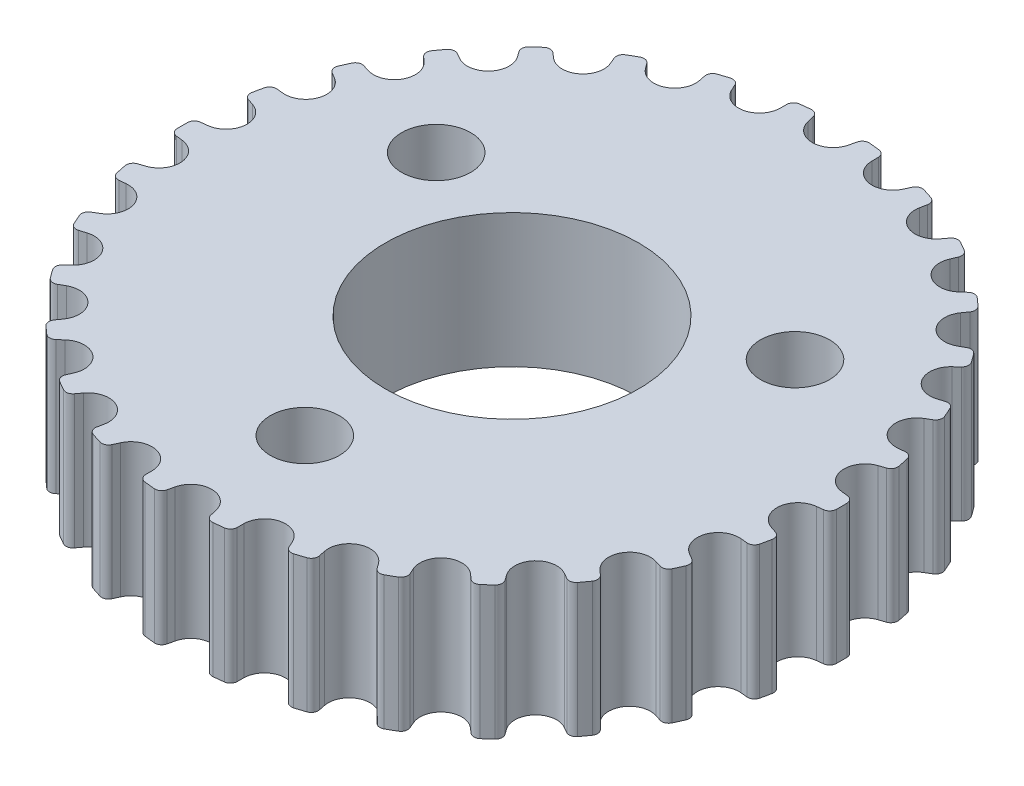
SolidWorks part; units mm, degrees
material "Acrylic (Medium-high impact)"
ref_plane "Front Plane" through (0, 0, 0) normal (0, 0, 1) x (1, 0, 0)
ref_plane "Top Plane" through (0, 0, 0) normal (0, 1, 0) x (1, 0, 0)
ref_plane "Right Plane" through (0, 0, 0) normal (1, 0, 0) x (0, 0, -1)
sketch "Sketch1" plane through (0, 0, 0) normal (0, 1, 0) x (1, 0, 0)
  circle A0 centre (0, 0) radius 14.3239
  dimension "D1" = 28.6479
extrude "Boss-Extrude1" add sketch "Sketch1" along normal blind 5.8
sketch "Sketch2" plane through (0, 5.8, 0) normal (0, 1, 0) x (1, 0, 0)
  line L0 (0, 0) -> (0, 14.3239) construction
  line L1 (-0.8883, 13.7564) -> (-0.95, 14.0339)
  line L2 (-2.9781, 14.0109) -> (-2.9781, 14.3239)
  line L3 (-2.9781, 14.3239) -> (2.9781, 14.3239)
  line L4 (0.8883, 13.7564) -> (0.95, 14.0339)
  line L5 (2.9781, 14.0109) -> (2.9781, 14.3239)
  circle A0 centre (0, 0) radius 14.3239 construction
  arc A1 (0.8883, 13.7564) -> (-0.8883, 13.7564) centre (0, 13.9539) cw
  arc A2 (-0.95, 14.0339) -> (-1.2694, 14.2676) centre (-1.2428, 13.9688) ccw
  arc A4 (0.95, 14.0339) -> (1.2694, 14.2676) centre (1.2428, 13.9688) cw
  arc A5 (-1.2694, 14.2676) -> (-2.9781, 14.0109) centre (0, 0) ccw
  arc A6 (1.2694, 14.2676) -> (2.9781, 14.0109) centre (0, 0) cw
  circle A8 centre (0, 0) radius 14.3239 construction
  point P11 (0, 14.3239)
  point P19 (0, 13.0439)
  dimension "D3" = 0.3
  dimension "D5" = 0.91
  dimension "D2" = 0.95
  dimension "D4" = 1.28
  dimension "D6" = 12
extrude "Cut-Extrude1" cut sketch "Sketch2" against normal through all
pattern_circular "CirPattern1" count 30 over 360 about axis through (0, 5.8, 0) along (0, -1, 0) of "Cut-Extrude1"
sketch "Sketch3" plane through (0, 0, 0) normal (0, -1, 0) x (1, 0, 0)
  circle A0 centre (0, 0) radius 5.5
  dimension "D1" = 11
extrude "Cut-Extrude2" cut sketch "Sketch3" against normal through all
sketch "Sketch4" plane through (0, 0, 0) normal (0, -1, 0) x (1, 0, 0)
  line L0 (0, 0) -> (0, 9) construction
  circle A0 centre (0, 9) radius 1.5
  circle A1 centre (7.7942, -4.5) radius 1.5
  circle A2 centre (-7.7942, -4.5) radius 1.5
  point P14 (0, 0)
  dimension "D1" = 3
  dimension "D2" = 9
  dimension "D3" = 3
extrude "Cut-Extrude3" cut sketch "Sketch4" against normal through all
sketch "Sketch5" plane through (0, 0, 0) normal (0, -1, 0) x (1, 0, 0)
  line L60 (8.7383, -10.682) -> (8.9513, -10.8702)
  line L61 (8.7383, -10.682) -> (8.9513, -10.8702)
  line L62 (9.875, -10.0385) -> (9.7101, -9.807)
  line L63 (9.875, -10.0385) -> (9.7101, -9.807)
  line L64 (12.5987, 6.2896) -> (12.3276, 6.2043)
  line L65 (12.5987, 6.2896) -> (12.3276, 6.2043)
  line L66 (11.5369, 7.5738) -> (11.7463, 7.766)
  line L67 (11.5369, 7.5738) -> (11.7463, 7.766)
  line L68 (-3.638, 13.3126) -> (-3.7561, 13.5712)
  line L69 (-3.638, 13.3126) -> (-3.7561, 13.5712)
  line L70 (-4.9382, 13.1871) -> (-4.8817, 12.9085)
  line L71 (-4.9382, 13.1871) -> (-4.8817, 12.9085)
  line L72 (-11.7463, 7.766) -> (-11.5369, 7.5738)
  line L73 (-11.7463, 7.766) -> (-11.5369, 7.5738)
  line L74 (-12.3276, 6.2043) -> (-12.5987, 6.2896)
  line L75 (-12.3276, 6.2043) -> (-12.5987, 6.2896)
  line L76 (-13.1043, 5.1541) -> (-12.8594, 5.0097)
  line L77 (-13.1043, 5.1541) -> (-12.8594, 5.0097)
  line L78 (-13.3481, 3.5057) -> (-13.6311, 3.5327)
  line L79 (-13.3481, 3.5057) -> (-13.6311, 3.5327)
  line L80 (-13.8895, 2.3169) -> (-13.62, 2.2266)
  line L81 (-13.8895, 2.3169) -> (-13.62, 2.2266)
  line L82 (-13.7853, 0.6538) -> (-14.0677, 0.6215)
  line L83 (-13.7853, 0.6538) -> (-14.0677, 0.6215)
  line L84 (-14.0677, -0.6215) -> (-13.7853, -0.6538)
  line L85 (-14.0677, -0.6215) -> (-13.7853, -0.6538)
  line L86 (-13.62, -2.2266) -> (-13.8895, -2.3169)
  line L87 (-13.62, -2.2266) -> (-13.8895, -2.3169)
  line L88 (-13.6311, -3.5327) -> (-13.3481, -3.5057)
  line L89 (-13.6311, -3.5327) -> (-13.3481, -3.5057)
  line L90 (-12.8594, -5.0097) -> (-13.1043, -5.1541)
  line L91 (-12.8594, -5.0097) -> (-13.1043, -5.1541)
  line L92 (-12.5987, -6.2896) -> (-12.3276, -6.2043)
  line L93 (-12.5987, -6.2896) -> (-12.3276, -6.2043)
  line L94 (-11.5369, -7.5738) -> (-11.7463, -7.766)
  line L95 (-11.5369, -7.5738) -> (-11.7463, -7.766)
  line L96 (-11.0157, -8.7716) -> (-10.7682, -8.6318)
  line L97 (-11.0157, -8.7716) -> (-10.7682, -8.6318)
  line L98 (-9.7101, -9.807) -> (-9.875, -10.0385)
  line L99 (-9.7101, -9.807) -> (-9.875, -10.0385)
  line L100 (-8.9513, -10.8702) -> (-8.7383, -10.682)
  line L101 (-8.9513, -10.8702) -> (-8.7383, -10.682)
  line L102 (-7.4589, -11.6115) -> (-7.5721, -11.8722)
  line L103 (-7.4589, -11.6115) -> (-7.5721, -11.8722)
  line L104 (-6.4956, -12.4937) -> (-6.3264, -12.2653)
  line L105 (-6.4956, -12.4937) -> (-6.3264, -12.2653)
  line L106 (-4.8817, -12.9085) -> (-4.9382, -13.1871)
  line L107 (-4.8817, -12.9085) -> (-4.9382, -13.1871)
  line L108 (-3.7561, -13.5712) -> (-3.638, -13.3126)
  line L109 (-3.7561, -13.5712) -> (-3.638, -13.3126)
  line L110 (-2.0912, -13.6414) -> (-2.0886, -13.9257)
  line L111 (-2.0912, -13.6414) -> (-2.0886, -13.9257)
  line L120 (6.3264, -12.2653) -> (6.4956, -12.4937)
  line L121 (7.5721, -11.8722) -> (7.4589, -11.6115)
  line L124 (10.7682, -8.6318) -> (11.0157, -8.7716)
  line L125 (11.7463, -7.766) -> (11.5369, -7.5738)
  line L126 (12.3276, -6.2043) -> (12.5987, -6.2896)
  line L127 (13.1043, -5.1541) -> (12.8594, -5.0097)
  line L128 (13.3481, -3.5057) -> (13.6311, -3.5327)
  line L129 (13.8895, -2.3169) -> (13.62, -2.2266)
  line L130 (13.7853, -0.6538) -> (14.0677, -0.6215)
  line L131 (14.0677, 0.6215) -> (13.7853, 0.6538)
  line L132 (13.62, 2.2266) -> (13.8895, 2.3169)
  line L133 (13.6311, 3.5327) -> (13.3481, 3.5057)
  line L134 (12.8594, 5.0097) -> (13.1043, 5.1541)
  line L137 (11.0157, 8.7716) -> (10.7682, 8.6318)
  line L138 (9.7101, 9.807) -> (9.875, 10.0385)
  line L139 (8.9513, 10.8702) -> (8.7383, 10.682)
  line L140 (7.4589, 11.6115) -> (7.5721, 11.8722)
  line L141 (6.4956, 12.4937) -> (6.3264, 12.2653)
  line L142 (4.8817, 12.9085) -> (4.9382, 13.1871)
  line L143 (3.7561, 13.5712) -> (3.638, 13.3126)
  line L144 (2.0912, 13.6414) -> (2.0886, 13.9257)
  line L145 (0.8524, 14.0556) -> (0.7907, 13.7781)
  line L146 (-0.7907, 13.7781) -> (-0.8524, 14.0556)
  line L147 (-2.0886, 13.9257) -> (-2.0912, 13.6414)
  line L150 (-6.3264, 12.2653) -> (-6.4956, 12.4937)
  line L151 (-7.5721, 11.8722) -> (-7.4589, 11.6115)
  line L152 (-8.7383, 10.682) -> (-8.9513, 10.8702)
  line L153 (-9.875, 10.0385) -> (-9.7101, 9.807)
  line L154 (-10.7682, 8.6318) -> (-11.0157, 8.7716)
  line L175 (-0.8524, -14.0556) -> (-0.7907, -13.7781)
  line L176 (0.7907, -13.7781) -> (0.8524, -14.0556)
  line L177 (2.0886, -13.9257) -> (2.0912, -13.6414)
  line L178 (3.638, -13.3126) -> (3.7561, -13.5712)
  line L179 (4.9382, -13.1871) -> (4.8817, -12.9085)
  line L180 (6.3264, -12.2653) -> (6.4956, -12.4937)
  line L181 (7.5721, -11.8722) -> (7.4589, -11.6115)
  line L184 (10.7682, -8.6318) -> (11.0157, -8.7716)
  line L185 (11.7463, -7.766) -> (11.5369, -7.5738)
  line L186 (12.3276, -6.2043) -> (12.5987, -6.2896)
  line L187 (13.1043, -5.1541) -> (12.8594, -5.0097)
  line L188 (13.3481, -3.5057) -> (13.6311, -3.5327)
  line L189 (13.8895, -2.3169) -> (13.62, -2.2266)
  line L190 (13.7853, -0.6538) -> (14.0677, -0.6215)
  line L191 (14.0677, 0.6215) -> (13.7853, 0.6538)
  line L192 (13.62, 2.2266) -> (13.8895, 2.3169)
  line L193 (13.6311, 3.5327) -> (13.3481, 3.5057)
  line L194 (12.8594, 5.0097) -> (13.1043, 5.1541)
  line L197 (11.0157, 8.7716) -> (10.7682, 8.6318)
  line L198 (9.7101, 9.807) -> (9.875, 10.0385)
  line L199 (8.9513, 10.8702) -> (8.7383, 10.682)
  line L200 (7.4589, 11.6115) -> (7.5721, 11.8722)
  line L201 (6.4956, 12.4937) -> (6.3264, 12.2653)
  line L202 (4.8817, 12.9085) -> (4.9382, 13.1871)
  line L203 (3.7561, 13.5712) -> (3.638, 13.3126)
  line L204 (2.0912, 13.6414) -> (2.0886, 13.9257)
  line L205 (0.8524, 14.0556) -> (0.7907, 13.7781)
  line L206 (-0.7907, 13.7781) -> (-0.8524, 14.0556)
  line L207 (-2.0886, 13.9257) -> (-2.0912, 13.6414)
  line L210 (-6.3264, 12.2653) -> (-6.4956, 12.4937)
  line L211 (-7.5721, 11.8722) -> (-7.4589, 11.6115)
  line L212 (-8.7383, 10.682) -> (-8.9513, 10.8702)
  line L213 (-9.875, 10.0385) -> (-9.7101, 9.807)
  line L214 (-10.7682, 8.6318) -> (-11.0157, 8.7716)
  line L235 (-0.8524, -14.0556) -> (-0.7907, -13.7781)
  line L236 (0.7907, -13.7781) -> (0.8524, -14.0556)
  line L237 (2.0886, -13.9257) -> (2.0912, -13.6414)
  line L238 (3.638, -13.3126) -> (3.7561, -13.5712)
  line L239 (4.9382, -13.1871) -> (4.8817, -12.9085)
  arc A76 (8.9513, -10.8702) -> (9.479, -10.8719) centre (9.2161, -10.5704) ccw
  arc A77 (8.9513, -10.8702) -> (9.479, -10.8719) centre (9.2161, -10.5704) ccw
  arc A78 (9.479, -10.8719) -> (9.8216, -10.5635) centre (0, 0) ccw
  arc A79 (9.479, -10.8719) -> (9.8216, -10.5635) centre (0, 0) ccw
  arc A80 (9.8216, -10.5635) -> (9.875, -10.0385) centre (9.5492, -10.2705) ccw
  arc A81 (9.8216, -10.5635) -> (9.875, -10.0385) centre (9.5492, -10.2705) ccw
  circle A120 centre (0, 0) radius 13.0439
  arc A121 (-0.8883, 13.7564) -> (0.8883, 13.7564) centre (0, 13.9539) ccw construction
  arc A128 (11.5369, 7.5738) -> (12.3276, 6.2043) centre (12.0845, 6.977) ccw
  arc A129 (11.5369, 7.5738) -> (12.3276, 6.2043) centre (12.0845, 6.977) ccw
  arc A130 (-3.7561, 13.5712) -> (-4.2375, 13.7875) centre (-4.12, 13.4051) ccw
  arc A131 (-3.7561, 13.5712) -> (-4.2375, 13.7875) centre (-4.12, 13.4051) ccw
  arc A132 (-4.2375, 13.7875) -> (-4.6759, 13.645) centre (0, 0) ccw
  arc A133 (-4.2375, 13.7875) -> (-4.6759, 13.645) centre (0, 0) ccw
  arc A134 (-4.6759, 13.645) -> (-4.9382, 13.1871) centre (-4.5462, 13.2666) ccw
  arc A135 (-4.6759, 13.645) -> (-4.9382, 13.1871) centre (-4.5462, 13.2666) ccw
  arc A136 (-11.8032, 8.2906) -> (-11.7463, 7.766) centre (-11.4759, 8.0607) ccw
  arc A137 (-11.8032, 8.2906) -> (-11.7463, 7.766) centre (-11.4759, 8.0607) ccw
  arc A138 (-12.3276, 6.2043) -> (-11.5369, 7.5738) centre (-12.0845, 6.977) ccw
  arc A139 (-12.3276, 6.2043) -> (-11.5369, 7.5738) centre (-12.0845, 6.977) ccw
  arc A140 (-12.5987, 6.2896) -> (-13.0815, 6.0766) centre (-12.7187, 5.908) ccw
  arc A141 (-12.5987, 6.2896) -> (-13.0815, 6.0766) centre (-12.7187, 5.908) ccw
  arc A142 (-13.0815, 6.0766) -> (-13.269, 5.6554) centre (0, 0) ccw
  arc A143 (-13.0815, 6.0766) -> (-13.269, 5.6554) centre (0, 0) ccw
  arc A144 (-13.269, 5.6554) -> (-13.1043, 5.1541) centre (-12.901, 5.4986) ccw
  arc A145 (-13.269, 5.6554) -> (-13.1043, 5.1541) centre (-12.901, 5.4986) ccw
  arc A146 (-13.3481, 3.5057) -> (-12.8594, 5.0097) centre (-13.271, 4.312) ccw
  arc A147 (-13.3481, 3.5057) -> (-12.8594, 5.0097) centre (-13.271, 4.312) ccw
  arc A148 (-13.6311, 3.5327) -> (-14.059, 3.224) centre (-13.6691, 3.1346) ccw
  arc A149 (-13.6311, 3.5327) -> (-14.059, 3.224) centre (-13.6691, 3.1346) ccw
  arc A150 (-14.059, 3.224) -> (-14.1549, 2.7731) centre (0, 0) ccw
  arc A151 (-14.059, 3.224) -> (-14.1549, 2.7731) centre (0, 0) ccw
  arc A152 (-14.1549, 2.7731) -> (-13.8895, 2.3169) centre (-13.7623, 2.6962) ccw
  arc A153 (-14.1549, 2.7731) -> (-13.8895, 2.3169) centre (-13.7623, 2.6962) ccw
  arc A154 (-13.7853, 0.6538) -> (-13.62, 2.2266) centre (-13.8775, 1.4586) ccw
  arc A155 (-13.7853, 0.6538) -> (-13.62, 2.2266) centre (-13.8775, 1.4586) ccw
  arc A156 (-14.0677, 0.6215) -> (-14.4221, 0.2305) centre (-14.0222, 0.2241) ccw
  arc A157 (-14.0677, 0.6215) -> (-14.4221, 0.2305) centre (-14.0222, 0.2241) ccw
  arc A158 (-14.4221, 0.2305) -> (-14.4221, -0.2305) centre (0, 0) ccw
  arc A159 (-14.4221, 0.2305) -> (-14.4221, -0.2305) centre (0, 0) ccw
  arc A160 (-14.4221, -0.2305) -> (-14.0677, -0.6215) centre (-14.0222, -0.2241) ccw
  arc A161 (-14.4221, -0.2305) -> (-14.0677, -0.6215) centre (-14.0222, -0.2241) ccw
  arc A162 (-13.62, -2.2266) -> (-13.7853, -0.6538) centre (-13.8775, -1.4586) ccw
  arc A163 (-13.62, -2.2266) -> (-13.7853, -0.6538) centre (-13.8775, -1.4586) ccw
  arc A164 (-13.8895, -2.3169) -> (-14.1549, -2.7731) centre (-13.7623, -2.6962) ccw
  arc A165 (-13.8895, -2.3169) -> (-14.1549, -2.7731) centre (-13.7623, -2.6962) ccw
  arc A166 (-14.1549, -2.7731) -> (-14.059, -3.224) centre (0, 0) ccw
  arc A167 (-14.1549, -2.7731) -> (-14.059, -3.224) centre (0, 0) ccw
  arc A168 (-14.059, -3.224) -> (-13.6311, -3.5327) centre (-13.6691, -3.1346) ccw
  arc A169 (-14.059, -3.224) -> (-13.6311, -3.5327) centre (-13.6691, -3.1346) ccw
  arc A170 (-12.8594, -5.0097) -> (-13.3481, -3.5057) centre (-13.271, -4.312) ccw
  arc A171 (-12.8594, -5.0097) -> (-13.3481, -3.5057) centre (-13.271, -4.312) ccw
  arc A172 (-13.1043, -5.1541) -> (-13.269, -5.6554) centre (-12.901, -5.4986) ccw
  arc A173 (-13.1043, -5.1541) -> (-13.269, -5.6554) centre (-12.901, -5.4986) ccw
  arc A174 (-13.269, -5.6554) -> (-13.0815, -6.0766) centre (0, 0) ccw
  arc A175 (-13.269, -5.6554) -> (-13.0815, -6.0766) centre (0, 0) ccw
  arc A176 (-13.0815, -6.0766) -> (-12.5987, -6.2896) centre (-12.7187, -5.908) ccw
  arc A177 (-13.0815, -6.0766) -> (-12.5987, -6.2896) centre (-12.7187, -5.908) ccw
  arc A178 (-11.5369, -7.5738) -> (-12.3276, -6.2043) centre (-12.0845, -6.977) ccw
  arc A179 (-11.5369, -7.5738) -> (-12.3276, -6.2043) centre (-12.0845, -6.977) ccw
  arc A180 (-11.7463, -7.766) -> (-11.8032, -8.2906) centre (-11.4759, -8.0607) ccw
  arc A181 (-11.7463, -7.766) -> (-11.8032, -8.2906) centre (-11.4759, -8.0607) ccw
  arc A182 (-11.8032, -8.2906) -> (-11.5323, -8.6636) centre (0, 0) ccw
  arc A183 (-11.8032, -8.2906) -> (-11.5323, -8.6636) centre (0, 0) ccw
  arc A184 (-11.5323, -8.6636) -> (-11.0157, -8.7716) centre (-11.2124, -8.4233) ccw
  arc A185 (-11.5323, -8.6636) -> (-11.0157, -8.7716) centre (-11.2124, -8.4233) ccw
  arc A186 (-9.7101, -9.807) -> (-10.7682, -8.6318) centre (-10.3698, -9.337) ccw
  arc A187 (-9.7101, -9.807) -> (-10.7682, -8.6318) centre (-10.3698, -9.337) ccw
  arc A188 (-9.875, -10.0385) -> (-9.8216, -10.5635) centre (-9.5492, -10.2705) ccw
  arc A189 (-9.875, -10.0385) -> (-9.8216, -10.5635) centre (-9.5492, -10.2705) ccw
  arc A190 (-9.8216, -10.5635) -> (-9.479, -10.8719) centre (0, 0) ccw
  arc A191 (-9.8216, -10.5635) -> (-9.479, -10.8719) centre (0, 0) ccw
  arc A192 (-9.479, -10.8719) -> (-8.9513, -10.8702) centre (-9.2161, -10.5704) ccw
  arc A193 (-9.479, -10.8719) -> (-8.9513, -10.8702) centre (-9.2161, -10.5704) ccw
  arc A194 (-7.4589, -11.6115) -> (-8.7383, -10.682) centre (-8.2019, -11.289) ccw
  arc A195 (-7.4589, -11.6115) -> (-8.7383, -10.682) centre (-8.2019, -11.289) ccw
  arc A196 (-7.5721, -11.8722) -> (-7.4107, -12.3747) centre (-7.2051, -12.0315) ccw
  arc A197 (-7.5721, -11.8722) -> (-7.4107, -12.3747) centre (-7.2051, -12.0315) ccw
  arc A198 (-7.4107, -12.3747) -> (-7.0114, -12.6052) centre (0, 0) ccw
  arc A199 (-7.4107, -12.3747) -> (-7.0114, -12.6052) centre (0, 0) ccw
  arc A200 (-7.0114, -12.6052) -> (-6.4956, -12.4937) centre (-6.817, -12.2556) ccw
  arc A201 (-7.0114, -12.6052) -> (-6.4956, -12.4937) centre (-6.817, -12.2556) ccw
  arc A202 (-4.8817, -12.9085) -> (-6.3264, -12.2653) centre (-5.6756, -12.7476) ccw
  arc A203 (-4.8817, -12.9085) -> (-6.3264, -12.2653) centre (-5.6756, -12.7476) ccw
  arc A204 (-4.9382, -13.1871) -> (-4.6759, -13.645) centre (-4.5462, -13.2666) ccw
  arc A205 (-4.9382, -13.1871) -> (-4.6759, -13.645) centre (-4.5462, -13.2666) ccw
  arc A206 (-4.6759, -13.645) -> (-4.2375, -13.7875) centre (0, 0) ccw
  arc A207 (-4.6759, -13.645) -> (-4.2375, -13.7875) centre (0, 0) ccw
  arc A208 (-4.2375, -13.7875) -> (-3.7561, -13.5712) centre (-4.12, -13.4051) ccw
  arc A209 (-4.2375, -13.7875) -> (-3.7561, -13.5712) centre (-4.12, -13.4051) ccw
  arc A210 (-2.0912, -13.6414) -> (-3.638, -13.3126) centre (-2.9012, -13.649) ccw
  arc A211 (-2.0912, -13.6414) -> (-3.638, -13.3126) centre (-2.9012, -13.649) ccw
  arc A212 (-2.0886, -13.9257) -> (-1.7367, -14.319) centre (-1.6886, -13.9219) ccw
  arc A213 (-2.0886, -13.9257) -> (-1.7367, -14.319) centre (-1.6886, -13.9219) ccw
  arc A214 (-1.7367, -14.319) -> (-1.2783, -14.3672) centre (0, 0) ccw
  arc A215 (-1.7367, -14.319) -> (-1.2783, -14.3672) centre (0, 0) ccw
  arc A240 (6.4956, -12.4937) -> (7.0114, -12.6052) centre (6.817, -12.2556) ccw
  arc A241 (7.0114, -12.6052) -> (7.4107, -12.3747) centre (0, 0) ccw
  arc A242 (7.4107, -12.3747) -> (7.5721, -11.8722) centre (7.2051, -12.0315) ccw
  arc A243 (8.7383, -10.682) -> (7.4589, -11.6115) centre (8.2019, -11.289) ccw
  arc A247 (10.7682, -8.6318) -> (9.7101, -9.807) centre (10.3698, -9.337) ccw
  arc A248 (11.0157, -8.7716) -> (11.5323, -8.6636) centre (11.2124, -8.4233) ccw
  arc A249 (11.5323, -8.6636) -> (11.8032, -8.2906) centre (0, 0) ccw
  arc A250 (11.8032, -8.2906) -> (11.7463, -7.766) centre (11.4759, -8.0607) ccw
  arc A251 (12.3276, -6.2043) -> (11.5369, -7.5738) centre (12.0845, -6.977) ccw
  arc A252 (12.5987, -6.2896) -> (13.0815, -6.0766) centre (12.7187, -5.908) ccw
  arc A253 (13.0815, -6.0766) -> (13.269, -5.6554) centre (0, 0) ccw
  arc A254 (13.269, -5.6554) -> (13.1043, -5.1541) centre (12.901, -5.4986) ccw
  arc A255 (13.3481, -3.5057) -> (12.8594, -5.0097) centre (13.271, -4.312) ccw
  arc A256 (13.6311, -3.5327) -> (14.059, -3.224) centre (13.6691, -3.1346) ccw
  arc A257 (14.059, -3.224) -> (14.1549, -2.7731) centre (0, 0) ccw
  arc A258 (14.1549, -2.7731) -> (13.8895, -2.3169) centre (13.7623, -2.6962) ccw
  arc A259 (13.7853, -0.6538) -> (13.62, -2.2266) centre (13.8775, -1.4586) ccw
  arc A260 (14.0677, -0.6215) -> (14.4221, -0.2305) centre (14.0222, -0.2241) ccw
  arc A261 (14.4221, -0.2305) -> (14.4221, 0.2305) centre (0, 0) ccw
  arc A262 (14.4221, 0.2305) -> (14.0677, 0.6215) centre (14.0222, 0.2241) ccw
  arc A263 (13.62, 2.2266) -> (13.7853, 0.6538) centre (13.8775, 1.4586) ccw
  arc A264 (13.8895, 2.3169) -> (14.1549, 2.7731) centre (13.7623, 2.6962) ccw
  arc A265 (14.1549, 2.7731) -> (14.059, 3.224) centre (0, 0) ccw
  arc A266 (14.059, 3.224) -> (13.6311, 3.5327) centre (13.6691, 3.1346) ccw
  arc A267 (12.8594, 5.0097) -> (13.3481, 3.5057) centre (13.271, 4.312) ccw
  arc A268 (13.1043, 5.1541) -> (13.269, 5.6554) centre (12.901, 5.4986) ccw
  arc A269 (13.269, 5.6554) -> (13.0815, 6.0766) centre (0, 0) ccw
  arc A270 (13.0815, 6.0766) -> (12.5987, 6.2896) centre (12.7187, 5.908) ccw
  arc A272 (11.7463, 7.766) -> (11.8032, 8.2906) centre (11.4759, 8.0607) ccw
  arc A273 (11.8032, 8.2906) -> (11.5323, 8.6636) centre (0, 0) ccw
  arc A274 (11.5323, 8.6636) -> (11.0157, 8.7716) centre (11.2124, 8.4233) ccw
  arc A275 (9.7101, 9.807) -> (10.7682, 8.6318) centre (10.3698, 9.337) ccw
  arc A276 (9.875, 10.0385) -> (9.8216, 10.5635) centre (9.5492, 10.2705) ccw
  arc A277 (9.8216, 10.5635) -> (9.479, 10.8719) centre (0, 0) ccw
  arc A278 (9.479, 10.8719) -> (8.9513, 10.8702) centre (9.2161, 10.5704) ccw
  arc A279 (7.4589, 11.6115) -> (8.7383, 10.682) centre (8.2019, 11.289) ccw
  arc A280 (7.5721, 11.8722) -> (7.4107, 12.3747) centre (7.2051, 12.0315) ccw
  arc A281 (7.4107, 12.3747) -> (7.0114, 12.6052) centre (0, 0) ccw
  arc A282 (7.0114, 12.6052) -> (6.4956, 12.4937) centre (6.817, 12.2556) ccw
  arc A283 (4.8817, 12.9085) -> (6.3264, 12.2653) centre (5.6756, 12.7476) ccw
  arc A284 (4.9382, 13.1871) -> (4.6759, 13.645) centre (4.5462, 13.2666) ccw
  arc A285 (4.6759, 13.645) -> (4.2375, 13.7875) centre (0, 0) ccw
  arc A286 (4.2375, 13.7875) -> (3.7561, 13.5712) centre (4.12, 13.4051) ccw
  arc A287 (2.0912, 13.6414) -> (3.638, 13.3126) centre (2.9012, 13.649) ccw
  arc A288 (2.0886, 13.9257) -> (1.7367, 14.319) centre (1.6886, 13.9219) ccw
  arc A289 (1.7367, 14.319) -> (1.2783, 14.3672) centre (0, 0) ccw
  arc A290 (1.2783, 14.3672) -> (0.8524, 14.0556) centre (1.2428, 13.9688) ccw
  arc A291 (-0.7907, 13.7781) -> (0.7907, 13.7781) centre (0, 13.9539) ccw
  arc A292 (-0.8524, 14.0556) -> (-1.2783, 14.3672) centre (-1.2428, 13.9688) ccw
  arc A293 (-1.2783, 14.3672) -> (-1.7367, 14.319) centre (0, 0) ccw
  arc A294 (-1.7367, 14.319) -> (-2.0886, 13.9257) centre (-1.6886, 13.9219) ccw
  arc A295 (-3.638, 13.3126) -> (-2.0912, 13.6414) centre (-2.9012, 13.649) ccw
  arc A299 (-6.3264, 12.2653) -> (-4.8817, 12.9085) centre (-5.6756, 12.7476) ccw
  arc A300 (-6.4956, 12.4937) -> (-7.0114, 12.6052) centre (-6.817, 12.2556) ccw
  arc A301 (-7.0114, 12.6052) -> (-7.4107, 12.3747) centre (0, 0) ccw
  arc A302 (-7.4107, 12.3747) -> (-7.5721, 11.8722) centre (-7.2051, 12.0315) ccw
  arc A303 (-8.7383, 10.682) -> (-7.4589, 11.6115) centre (-8.2019, 11.289) ccw
  arc A304 (-8.9513, 10.8702) -> (-9.479, 10.8719) centre (-9.2161, 10.5704) ccw
  arc A305 (-9.479, 10.8719) -> (-9.8216, 10.5635) centre (0, 0) ccw
  arc A306 (-9.8216, 10.5635) -> (-9.875, 10.0385) centre (-9.5492, 10.2705) ccw
  arc A307 (-10.7682, 8.6318) -> (-9.7101, 9.807) centre (-10.3698, 9.337) ccw
  arc A308 (-11.0157, 8.7716) -> (-11.5323, 8.6636) centre (-11.2124, 8.4233) ccw
  arc A309 (-11.5323, 8.6636) -> (-11.8032, 8.2906) centre (0, 0) ccw
  arc A350 (-1.2783, -14.3672) -> (-0.8524, -14.0556) centre (-1.2428, -13.9688) ccw
  arc A351 (0.7907, -13.7781) -> (-0.7907, -13.7781) centre (0, -13.9539) ccw
  arc A352 (0.8524, -14.0556) -> (1.2783, -14.3672) centre (1.2428, -13.9688) ccw
  arc A353 (1.2783, -14.3672) -> (1.7367, -14.319) centre (0, 0) ccw
  arc A354 (1.7367, -14.319) -> (2.0886, -13.9257) centre (1.6886, -13.9219) ccw
  arc A355 (3.638, -13.3126) -> (2.0912, -13.6414) centre (2.9012, -13.649) ccw
  arc A356 (3.7561, -13.5712) -> (4.2375, -13.7875) centre (4.12, -13.4051) ccw
  arc A357 (4.2375, -13.7875) -> (4.6759, -13.645) centre (0, 0) ccw
  arc A358 (4.6759, -13.645) -> (4.9382, -13.1871) centre (4.5462, -13.2666) ccw
  arc A359 (6.3264, -12.2653) -> (4.8817, -12.9085) centre (5.6756, -12.7476) ccw
  arc A360 (6.4956, -12.4937) -> (7.0114, -12.6052) centre (6.817, -12.2556) ccw
  arc A361 (7.0114, -12.6052) -> (7.4107, -12.3747) centre (0, 0) ccw
  arc A362 (7.4107, -12.3747) -> (7.5721, -11.8722) centre (7.2051, -12.0315) ccw
  arc A363 (8.7383, -10.682) -> (7.4589, -11.6115) centre (8.2019, -11.289) ccw
  arc A367 (10.7682, -8.6318) -> (9.7101, -9.807) centre (10.3698, -9.337) ccw
  arc A368 (11.0157, -8.7716) -> (11.5323, -8.6636) centre (11.2124, -8.4233) ccw
  arc A369 (11.5323, -8.6636) -> (11.8032, -8.2906) centre (0, 0) ccw
  arc A370 (11.8032, -8.2906) -> (11.7463, -7.766) centre (11.4759, -8.0607) ccw
  arc A371 (12.3276, -6.2043) -> (11.5369, -7.5738) centre (12.0845, -6.977) ccw
  arc A372 (12.5987, -6.2896) -> (13.0815, -6.0766) centre (12.7187, -5.908) ccw
  arc A373 (13.0815, -6.0766) -> (13.269, -5.6554) centre (0, 0) ccw
  arc A374 (13.269, -5.6554) -> (13.1043, -5.1541) centre (12.901, -5.4986) ccw
  arc A375 (13.3481, -3.5057) -> (12.8594, -5.0097) centre (13.271, -4.312) ccw
  arc A376 (13.6311, -3.5327) -> (14.059, -3.224) centre (13.6691, -3.1346) ccw
  arc A377 (14.059, -3.224) -> (14.1549, -2.7731) centre (0, 0) ccw
  arc A378 (14.1549, -2.7731) -> (13.8895, -2.3169) centre (13.7623, -2.6962) ccw
  arc A379 (13.7853, -0.6538) -> (13.62, -2.2266) centre (13.8775, -1.4586) ccw
  arc A380 (14.0677, -0.6215) -> (14.4221, -0.2305) centre (14.0222, -0.2241) ccw
  arc A381 (14.4221, -0.2305) -> (14.4221, 0.2305) centre (0, 0) ccw
  arc A382 (14.4221, 0.2305) -> (14.0677, 0.6215) centre (14.0222, 0.2241) ccw
  arc A383 (13.62, 2.2266) -> (13.7853, 0.6538) centre (13.8775, 1.4586) ccw
  arc A384 (13.8895, 2.3169) -> (14.1549, 2.7731) centre (13.7623, 2.6962) ccw
  arc A385 (14.1549, 2.7731) -> (14.059, 3.224) centre (0, 0) ccw
  arc A386 (14.059, 3.224) -> (13.6311, 3.5327) centre (13.6691, 3.1346) ccw
  arc A387 (12.8594, 5.0097) -> (13.3481, 3.5057) centre (13.271, 4.312) ccw
  arc A388 (13.1043, 5.1541) -> (13.269, 5.6554) centre (12.901, 5.4986) ccw
  arc A389 (13.269, 5.6554) -> (13.0815, 6.0766) centre (0, 0) ccw
  arc A390 (13.0815, 6.0766) -> (12.5987, 6.2896) centre (12.7187, 5.908) ccw
  arc A392 (11.7463, 7.766) -> (11.8032, 8.2906) centre (11.4759, 8.0607) ccw
  arc A393 (11.8032, 8.2906) -> (11.5323, 8.6636) centre (0, 0) ccw
  arc A394 (11.5323, 8.6636) -> (11.0157, 8.7716) centre (11.2124, 8.4233) ccw
  arc A395 (9.7101, 9.807) -> (10.7682, 8.6318) centre (10.3698, 9.337) ccw
  arc A396 (9.875, 10.0385) -> (9.8216, 10.5635) centre (9.5492, 10.2705) ccw
  arc A397 (9.8216, 10.5635) -> (9.479, 10.8719) centre (0, 0) ccw
  arc A398 (9.479, 10.8719) -> (8.9513, 10.8702) centre (9.2161, 10.5704) ccw
  arc A399 (7.4589, 11.6115) -> (8.7383, 10.682) centre (8.2019, 11.289) ccw
  arc A400 (7.5721, 11.8722) -> (7.4107, 12.3747) centre (7.2051, 12.0315) ccw
  arc A401 (7.4107, 12.3747) -> (7.0114, 12.6052) centre (0, 0) ccw
  arc A402 (7.0114, 12.6052) -> (6.4956, 12.4937) centre (6.817, 12.2556) ccw
  arc A403 (4.8817, 12.9085) -> (6.3264, 12.2653) centre (5.6756, 12.7476) ccw
  arc A404 (4.9382, 13.1871) -> (4.6759, 13.645) centre (4.5462, 13.2666) ccw
  arc A405 (4.6759, 13.645) -> (4.2375, 13.7875) centre (0, 0) ccw
  arc A406 (4.2375, 13.7875) -> (3.7561, 13.5712) centre (4.12, 13.4051) ccw
  arc A407 (2.0912, 13.6414) -> (3.638, 13.3126) centre (2.9012, 13.649) ccw
  arc A408 (2.0886, 13.9257) -> (1.7367, 14.319) centre (1.6886, 13.9219) ccw
  arc A409 (1.7367, 14.319) -> (1.2783, 14.3672) centre (0, 0) ccw
  arc A410 (1.2783, 14.3672) -> (0.8524, 14.0556) centre (1.2428, 13.9688) ccw
  arc A411 (-0.7907, 13.7781) -> (0.7907, 13.7781) centre (0, 13.9539) ccw
  arc A412 (-0.8524, 14.0556) -> (-1.2783, 14.3672) centre (-1.2428, 13.9688) ccw
  arc A413 (-1.2783, 14.3672) -> (-1.7367, 14.319) centre (0, 0) ccw
  arc A414 (-1.7367, 14.319) -> (-2.0886, 13.9257) centre (-1.6886, 13.9219) ccw
  arc A415 (-3.638, 13.3126) -> (-2.0912, 13.6414) centre (-2.9012, 13.649) ccw
  arc A419 (-6.3264, 12.2653) -> (-4.8817, 12.9085) centre (-5.6756, 12.7476) ccw
  arc A420 (-6.4956, 12.4937) -> (-7.0114, 12.6052) centre (-6.817, 12.2556) ccw
  arc A421 (-7.0114, 12.6052) -> (-7.4107, 12.3747) centre (0, 0) ccw
  arc A422 (-7.4107, 12.3747) -> (-7.5721, 11.8722) centre (-7.2051, 12.0315) ccw
  arc A423 (-8.7383, 10.682) -> (-7.4589, 11.6115) centre (-8.2019, 11.289) ccw
  arc A424 (-8.9513, 10.8702) -> (-9.479, 10.8719) centre (-9.2161, 10.5704) ccw
  arc A425 (-9.479, 10.8719) -> (-9.8216, 10.5635) centre (0, 0) ccw
  arc A426 (-9.8216, 10.5635) -> (-9.875, 10.0385) centre (-9.5492, 10.2705) ccw
  arc A427 (-10.7682, 8.6318) -> (-9.7101, 9.807) centre (-10.3698, 9.337) ccw
  arc A428 (-11.0157, 8.7716) -> (-11.5323, 8.6636) centre (-11.2124, 8.4233) ccw
  arc A429 (-11.5323, 8.6636) -> (-11.8032, 8.2906) centre (0, 0) ccw
  arc A470 (-1.2783, -14.3672) -> (-0.8524, -14.0556) centre (-1.2428, -13.9688) ccw
  arc A471 (0.7907, -13.7781) -> (-0.7907, -13.7781) centre (0, -13.9539) ccw
  arc A472 (0.8524, -14.0556) -> (1.2783, -14.3672) centre (1.2428, -13.9688) ccw
  arc A473 (1.2783, -14.3672) -> (1.7367, -14.319) centre (0, 0) ccw
  arc A474 (1.7367, -14.319) -> (2.0886, -13.9257) centre (1.6886, -13.9219) ccw
  arc A475 (3.638, -13.3126) -> (2.0912, -13.6414) centre (2.9012, -13.649) ccw
  arc A476 (3.7561, -13.5712) -> (4.2375, -13.7875) centre (4.12, -13.4051) ccw
  arc A477 (4.2375, -13.7875) -> (4.6759, -13.645) centre (0, 0) ccw
  arc A478 (4.6759, -13.645) -> (4.9382, -13.1871) centre (4.5462, -13.2666) ccw
  arc A479 (6.3264, -12.2653) -> (4.8817, -12.9085) centre (5.6756, -12.7476) ccw
  dimension "D1" = 0.1
extrude "Boss-Extrude2" [suppressed] add sketch "Sketch5" against normal up to surface (5.8 mm away) up to face at (7.7942, 5.8, -6)
equation "\"smallPulleyTeeth\"= 15"
equation "\"largePulleyTeeth\"= 30"
equation "\"eighthThick\"= 2.9mm"
equation "\"D1@Sketch1\"=3*\"largePulleyTeeth\"/pi"
equation "\"D1@Boss-Extrude1\" = \"eighthThick\" * 2"
equation "\"D6@Sketch2\"=360/\"largePulleyTeeth\""
equation "\"quarterThick\"=6.0mm"
equation "\"D1@CirPattern1\"=\"largePulleyTeeth\""
equation "\"sixteenthThick\" = 1.7mm"
equation "\"OD\" = 146mm"
equation "\"puckAngle\" = 60.5deg"
equation "\"puckDiam\" = 76.5mm"
equation "\"axlePress\" = 5.9mm"
equation "\"press\" = 0.2mm"
equation "\"wheelClear\" = 0.3mm"
equation "\"10-32clear\" = 4.8mm"
equation "\"D1@Sketch4\"=\"4-40clear\""
equation "\"6-32clear\" = 3.3mm"
equation "\"8-32clear\" = 4.0mm"
equation "\"4-40clear\" = 3.0mm"
equation "\"wheelHeight\" = 22mm"
equation "\"wheelWell\" = 65mm"
